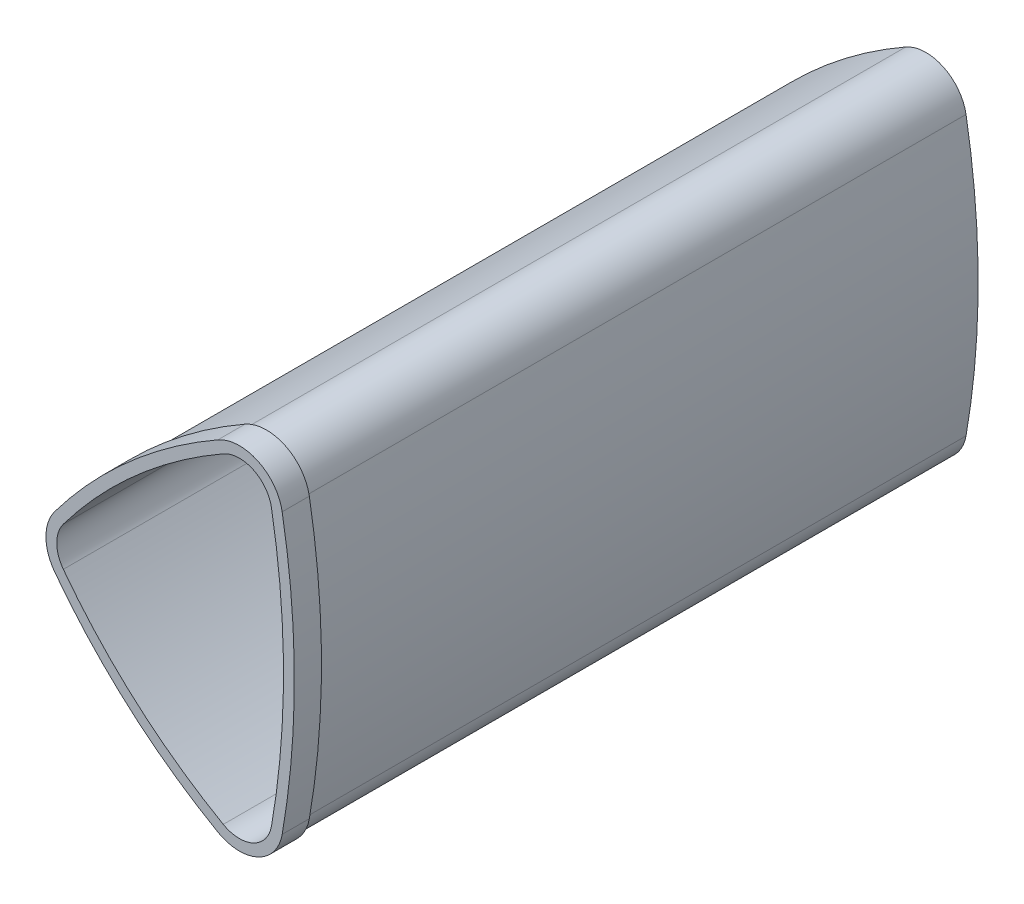
SolidWorks part; units mm, degrees
material "AISI 304"
ref_plane "Front Plane" through (0, 0, 0) normal (1, 0, 0) x (0, 1, 0)
ref_plane "Top Plane" through (0, 0, 0) normal (0, 0, 1) x (0, 1, 0)
ref_plane "Right Plane" through (0, 0, 0) normal (0, 1, 0) x (-1, 0, 0)
sketch "Sketch1" plane through (0, 0, 0) normal (0, 0, 1) x (0, 1, 0)
  line L0 (0, 208.2686) -> (0, -170.1263) construction
  circle A0 centre (0, 0) radius 12.5
  arc A1 (-50.7828, -19.1096) -> (50.7828, -19.1096) centre (0, 270.4713) ccw
  arc A2 (-59.1349, -1.3467) -> (-50.7828, -19.1096) centre (-48.71, -7.29) ccw
  arc A3 (-62.6098, 0.6344) -> (-9.6176, 60.8068) centre (109.4003, -97.4296) cw
  arc A4 (7.2132, 57.6101) -> (-7.2132, 57.6101) centre (0, 48.02) ccw
  arc A5 (59.1349, -1.3467) -> (50.7828, -19.1096) centre (48.71, -7.29) cw
  arc A6 (59.1349, -1.3467) -> (7.2132, 57.6101) centre (-109.4003, -97.4296) ccw
  arc A7 (-59.1349, -1.3467) -> (-7.2132, 57.6101) centre (109.4003, -97.4296) cw
  arc A8 (9.6176, 60.8068) -> (-9.6176, 60.8068) centre (0, 48.02) ccw
  arc A9 (62.6098, 0.6344) -> (9.6176, 60.8068) centre (-109.4003, -97.4296) ccw
  arc A10 (62.6098, 0.6344) -> (51.4737, -23.0495) centre (48.71, -7.29) cw
  arc A11 (-51.4737, -23.0495) -> (51.4737, -23.0495) centre (0, 270.4713) ccw
  arc A12 (-62.6098, 0.6344) -> (-51.4737, -23.0495) centre (-48.71, -7.29) ccw
  arc A13 (-61.7411, 0.1391) -> (-9.0165, 60.0076) centre (109.4003, -97.4296) cw
  arc A14 (9.0165, 60.0076) -> (-9.0165, 60.0076) centre (0, 48.02) ccw
  arc A15 (61.7411, 0.1391) -> (9.0165, 60.0076) centre (-109.4003, -97.4296) ccw
  arc A16 (61.7411, 0.1391) -> (51.301, -22.0645) centre (48.71, -7.29) cw
  arc A17 (-51.301, -22.0645) -> (51.301, -22.0645) centre (0, 270.4713) ccw
  arc A18 (-61.7411, 0.1391) -> (-51.301, -22.0645) centre (-48.71, -7.29) ccw
  dimension "D1" = 25
  dimension "D2" = 48.71
  dimension "D3" = 24
  dimension "D4" = 194
  dimension "D5" = 24
  dimension "D8" = 294
  dimension "D9" = 4
  dimension "D6" = 48.02
  dimension "D7" = 7.29
  dimension "D10" = 3
extrude "Boss-Extrude1" add sketch "Sketch1" along normal blind 3 contours A13 A14 A15 A16 A17 A18 | A0
extrude "Boss-Extrude2" add sketch "Sketch1<3>" along normal blind 250 from surface contours L0 A14 A13 A18 A17 A1 A2 A7 A4 | A14 L0 A4 A6 A5 A1 A17 A16 A15 region at (-61.2046, 4.405, 0) region at (-61.52, -1.099, 0) starting at face at (-12.4477, 0, 3)
sketch "Sketch1<3>" plane through (0, 0, 0) normal (0, 0, 1) x (0, 1, 0) same geometry as "Sketch1"
extrude "Boss-Extrude3" add sketch "Sketch1<4>" against normal blind 10 from surface contours L0 A8 A3 A12 A11 A17 A18 A13 A14 | A8 L0 A14 A15 A16 A17 A11 A10 A9 region at (-63.0891, 5.0346, 0) region at (-63.52, -1.1211, 0) starting at face at (-12.4477, 0, 253)
sketch "Sketch1<4>" plane through (0, 0, 0) normal (0, 0, 1) x (0, 1, 0) same geometry as "Sketch1"
